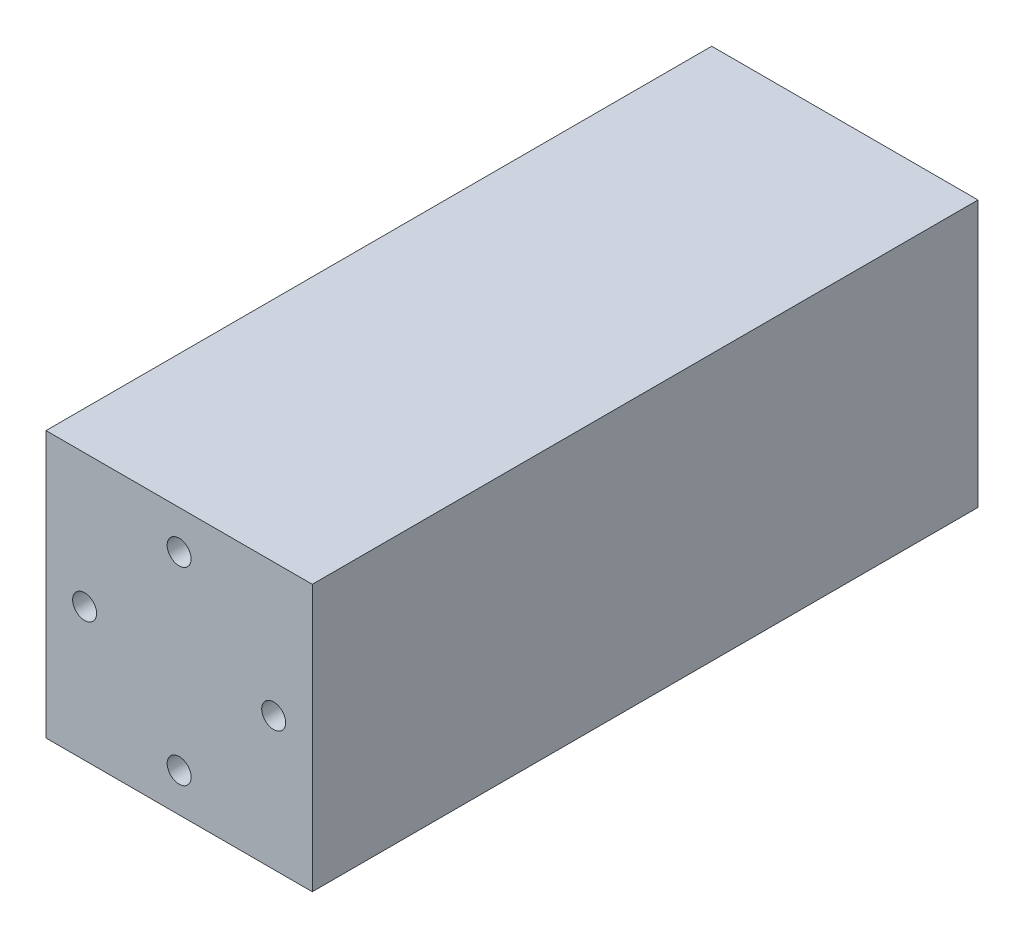
SolidWorks part; units mm, degrees
ref_plane "前视基准面" through (0, 0, 0) normal (0, 0, 1) x (1, 0, 0)
ref_plane "上视基准面" through (0, 0, 0) normal (0, 1, 0) x (1, 0, 0)
ref_plane "右视基准面" through (0, 0, 0) normal (1, 0, 0) x (0, 0, -1)
other "Configuration Table"
sketch "草图1" plane through (0, 0, 0) normal (0, 0, 1) x (1, 0, 0)
  line L1 (-8.8, -8.8) -> (8.8, -8.8)
  line L2 (-8.8, -8.8) -> (-8.8, 8.8)
  line L3 (-8.8, 8.8) -> (8.8, 8.8)
  line L4 (8.8, -8.8) -> (8.8, 8.8)
  line L5 (-8.8, -8.8) -> (8.8, 8.8) construction
  line L6 (-8.8, 8.8) -> (8.8, -8.8) construction
  line L7 (-10, -10) -> (10, -10)
  line L8 (-10, -10) -> (-10, 10)
  line L9 (-10, 10) -> (10, 10)
  line L10 (10, -10) -> (10, 10)
  line L11 (-10, -10) -> (10, 10) construction
  line L12 (-10, 10) -> (10, -10) construction
  circle A0 centre (0, 7.1) radius 1.7
  circle A1 centre (-7.1, 0) radius 1.7
  circle A2 centre (0, -7.1) radius 1.7
  circle A3 centre (7.1, 0) radius 1.7
  circle A4 centre (-7.1, 0) radius 0.9
  circle A5 centre (0, 7.1) radius 0.9
  circle A6 centre (7.1, 0) radius 0.9
  circle A7 centre (0, -7.1) radius 0.9
  point P0 (0, 0)
  point P16 (0, 0)
  dimension "D2" = 3.4
  dimension "D4" = 1.8
  dimension "D1" = 17.6
  dimension "D3" = 20
extrude "凸台-拉伸1" add sketch "草图1" along normal blind 50 contours L9 L10 L7 L8
extrude "切除-拉伸1" cut sketch "草图1<3>" along normal blind 3 contours A5 | A4 | A6 | A7
sketch "草图1<3>" plane through (0, 0, 0) normal (0, 0, 1) x (1, 0, 0) same geometry as "草图1"
extrude "切除-拉伸2" cut sketch "草图1<4>" against normal blind 3 from surface contours A5 | A4 | A6 | A7 starting at face at (0, 0, 50)
sketch "草图1<4>" plane through (0, 0, 0) normal (0, 0, 1) x (1, 0, 0) same geometry as "草图1"
